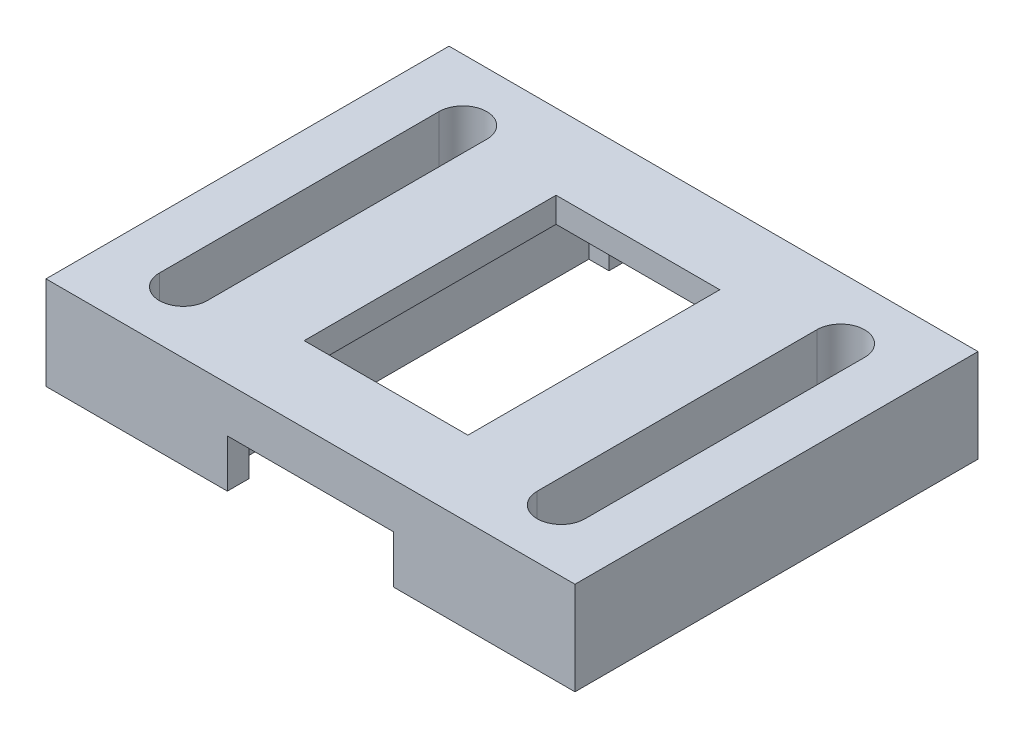
SolidWorks part; units mm, degrees
ref_plane "Front Plane" through (0, 0, 0) normal (0, 0, 1) x (1, 0, 0)
ref_plane "Top Plane" through (0, 0, 0) normal (0, 1, 0) x (1, 0, 0)
ref_plane "Right Plane" through (0, 0, 0) normal (1, 0, 0) x (0, 0, -1)
ref_axis "X-Axis" through (-88.99, 0, 0) along (1, 0, 0)
ref_axis "Y-Axis" through (0, 55, 0) along (0, -1, 0)
ref_axis "Z-Axis" through (0, 0, -88.99) along (0, 0, 1)
sketch "Sketch1" plane through (0, 0, 0) normal (0, 1, 0) x (1, 0, 0)
  line L1 (-5, 8) -> (5, 8)
  line L2 (-5, 8) -> (-5, -8)
  line L3 (-5, -8) -> (5, -8)
  line L4 (5, 8) -> (5, -8)
  line L5 (-5, 8) -> (5, -8) construction
  line L6 (-5, -8) -> (5, 8) construction
  point P0 (0, 0)
  dimension "D1" = 16
  dimension "D2" = 10
extrude "Boss-Extrude1" add sketch "Sketch1" along normal blind 3.7
sketch "Sketch2" plane through (0, 0, 0) normal (0, -1, 0) x (1, 0, 0)
  line L1 (-4.1, -7.15) -> (4.1, -7.15)
  line L2 (-4.1, -7.15) -> (-4.1, 7.15)
  line L3 (-4.1, 7.15) -> (4.1, 7.15)
  line L4 (4.1, -7.15) -> (4.1, 7.15)
  line L5 (-4.1, -7.15) -> (4.1, 7.15) construction
  line L6 (-4.1, 7.15) -> (4.1, -7.15) construction
  point P0 (0, 0)
  dimension "D1" = 14.3
  dimension "D2" = 8.2
extrude "Cut-Extrude1" cut sketch "Sketch2" against normal blind 2.7
sketch "Sketch3" plane through (0, 0, 0) normal (0, -1, 0) x (1, 0, 0)
  line L0 (-5, 8) -> (5, 8) construction
  line L1 (3.3, -8) -> (-3.3, -8)
  line L2 (3.3, -8) -> (3.3, 8)
  line L3 (3.3, 8) -> (-3.3, 8)
  line L4 (-3.3, -8) -> (-3.3, 8)
  line L5 (3.3, -8) -> (-3.3, 8) construction
  line L6 (3.3, 8) -> (-3.3, -8) construction
  line L8 (-4.1, 7.15) -> (-4.1, -7.15) construction
  point P0 (0, 0)
  dimension "D1" = 0.8
extrude "Cut-Extrude2" cut sketch "Sketch3" against normal offset from surface (1.9 mm away) 0.8 up to face at (0, 2.7, 0)
sketch "Sketch4" plane through (0, 3.7, 0) normal (0, 1, 0) x (1, 0, 0)
  line L1 (-3.25, -5) -> (3.25, -5)
  line L2 (-3.25, -5) -> (-3.25, 5)
  line L3 (-3.25, 5) -> (3.25, 5)
  line L4 (3.25, -5) -> (3.25, 5)
  line L5 (-3.25, -5) -> (3.25, 5) construction
  line L6 (-3.25, 5) -> (3.25, -5) construction
  point P0 (0, 0)
  dimension "D1" = 6.5
  dimension "D2" = 10
extrude "Cut-Extrude3" cut sketch "Sketch4" against normal up to next
sketch "Sketch5" plane through (0, 0, 0) normal (0, -1, 0) x (1, 0, 0)
  line L1 (-10.5, 8) -> (-5, 8)
  line L2 (-10.5, 8) -> (-10.5, -8)
  line L3 (-10.5, -8) -> (-5, -8)
  line L4 (-5, 8) -> (-5, -8)
  dimension "D1" = 5.5
extrude "Boss-Extrude2" add sketch "Sketch5" against normal blind 3.7
sketch "Sketch6" plane through (0, 3.7, 0) normal (0, 1, 0) x (1, 0, 0)
  line L0 (-7.5, 6.5) -> (-7.5, -6.5) construction
  line L3 (-7.5, 5.55) -> (-7.5, -5.55) construction
  line L4 (-6.55, 5.55) -> (-6.55, -5.55)
  line L5 (-8.45, 5.55) -> (-8.45, -5.55)
  line L6 (-7.5, 6.5) -> (-7.5, 8) construction
  line L7 (-7.5, -6.5) -> (-7.5, -8) construction
  line L8 (-10.5, -8) -> (-10.5, 8) construction
  arc A0 (-6.55, 5.55) -> (-8.45, 5.55) centre (-7.5, 5.55) ccw
  arc A1 (-8.45, -5.55) -> (-6.55, -5.55) centre (-7.5, -5.55) ccw
  point P8 (-7.5, 0)
  dimension "D2" = 0.95
  dimension "D1" = 1.5
  dimension "D3" = 3
extrude "Cut-Extrude4" cut sketch "Sketch6" against normal through all
mirror "Mirror1" about plane through (0, 0, 0) normal (1, 0, 0) of "Cut-Extrude4", "Boss-Extrude2"
equation "\"D2@Sketch6\"=1.90mm/2"
